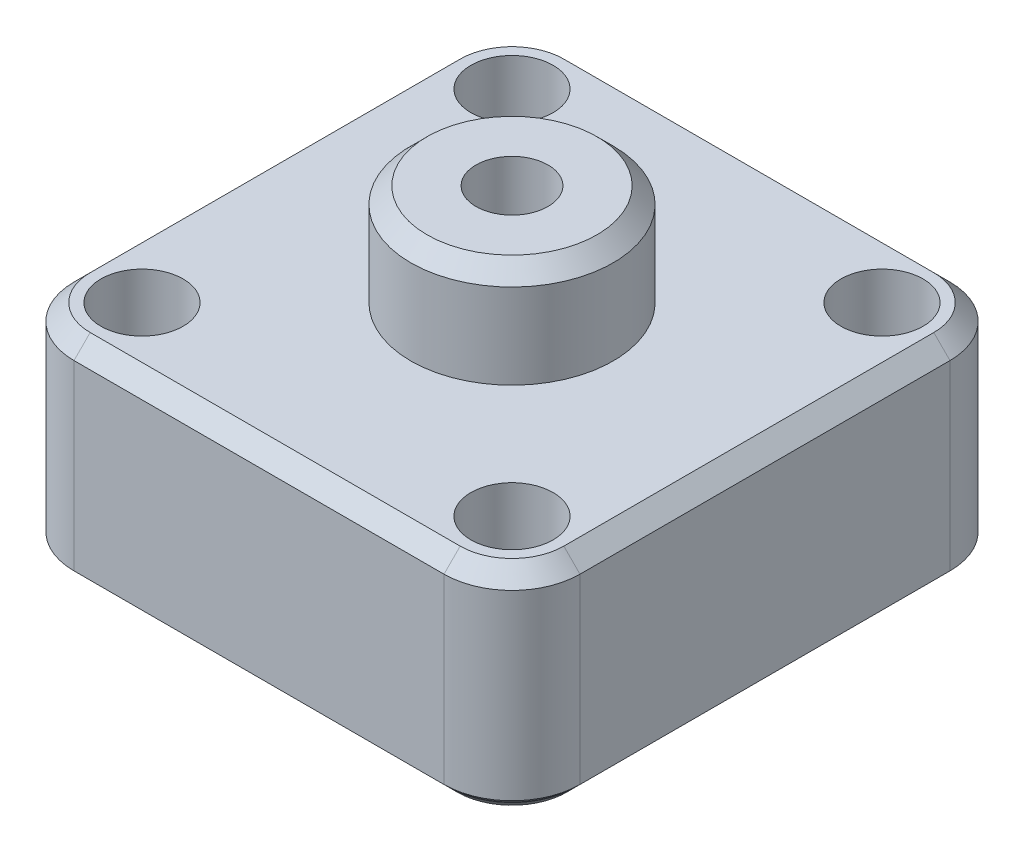
SolidWorks part; units mm, degrees
ref_plane "Front Plane" through (0, 0, 0) normal (0, 0, 1) x (1, 0, 0)
ref_plane "Top Plane" through (0, 0, 0) normal (0, 1, 0) x (1, 0, 0)
ref_plane "Right Plane" through (0, 0, 0) normal (1, 0, 0) x (0, 0, -1)
sketch "Sketch1" plane through (0, 0, 0) normal (0, 1, 0) x (1, 0, 0)
  line L1 (-7.9375, 7.9375) -> (7.9375, 7.9375)
  line L2 (-7.9375, 7.9375) -> (-7.9375, -7.9375)
  line L3 (-7.9375, -7.9375) -> (7.9375, -7.9375)
  line L4 (7.9375, 7.9375) -> (7.9375, -7.9375)
  line L5 (-7.9375, 7.9375) -> (7.9375, -7.9375) construction
  line L6 (-7.9375, -7.9375) -> (7.9375, 7.9375) construction
  point P0 (0, 0)
  dimension "D1" = 15.875
  dimension "D2" = 15.875
extrude "Boss-Extrude1" add sketch "Sketch1" along normal blind 9.525
hole_wizard "#5-40 Tapped Hole1" positions "Sketch2" profile "Sketch3" tap size "#5-40" standard "ANSI Inch" end condition through all
sketch "Sketch2" plane through (0, 0, 0) normal (0, -1, 0) x (-1, 0, 0)
  line L0 (-5.8039, 5.8039) -> (5.8039, -5.8039) construction
  point P0 (-5.8039, -5.8039)
  point P2 (-5.8039, 5.8039)
  point P4 (5.8039, 5.8039)
  point P6 (5.8039, -5.8039)
  dimension "D1" = 11.6078
  dimension "D2" = 11.6078
sketch "Sketch3" plane through (5.8039, 0, 5.8039) normal (1, 0, 0) x (0, 0, -1)
  line L0 (0, 0) -> (0, 9.525)
  line L1 (0, 9.525) -> (1.289, 9.525)
  line L2 (1.289, 9.525) -> (1.289, 0)
  line L5 (1.289, 0) -> (0, 0)
  line L11 (0, -6.35) -> (0, 107.95) construction
  dimension "Thru Tap Drill Dia." = 2.5781
  dimension "Thru Tap Drill Depth" = 9.525
cosmetic thread "Hole Thread1" parameters "D2"=3.175
cosmetic thread "Hole Thread2" parameters "D2"=3.175
cosmetic thread "Hole Thread3" parameters "D2"=3.175
cosmetic thread "Hole Thread4" parameters "D2"=3.175
sketch "Sketch4" plane through (0, 0, 0) normal (0, -1, 0) x (1, 0, 0)
  circle A0 centre (0, 0) radius 3.937
  dimension "D1" = 7.874
extrude "Boss-Extrude2" add sketch "Sketch4" along normal blind 1.143
sketch "Sketch10" plane through (0, -1.143, 0) normal (0, -1, 0) x (1, 0, 0)
  circle A0 centre (0, 0) radius 1.9685
  dimension "D1" = 3.937
extrude "Boss-Extrude4" add sketch "Sketch10" along normal offset from surface (4.953 mm away) 6.096 up to face at (0, 0, 3.937) offset beyond the face yes
hole_wizard "#4-40 Tapped Hole1" positions "Sketch5" profile "Sketch6" tap size "#4-40" standard "ANSI Inch" end condition through all
sketch "Sketch5" plane through (0, -6.096, 0) normal (0, -1, 0) x (-1, 0, 0)
  point P0 (0, 0)
sketch "Sketch6" plane through (0, -6.096, 0) normal (1, 0, 0) x (0, 0, -1)
  line L0 (0, 0) -> (0, 15.621)
  line L1 (0, 15.621) -> (1.1303, 15.621)
  line L2 (1.1303, 15.621) -> (1.1303, 0)
  line L5 (1.1303, 0) -> (0, 0)
  line L11 (0, -6.35) -> (0, 107.95) construction
  dimension "Thru Tap Drill Dia." = 2.2606
  dimension "Thru Tap Drill Depth" = 15.621
cosmetic thread "Hole Thread6" parameters "D2"=2.8448
sketch "Sketch8" plane through (0, 9.525, 0) normal (0, 1, 0) x (1, 0, 0)
  arc A0 (-3.8971, 8.3426) -> (-8.3426, 3.8971) centre (-5.8039, 5.8039) ccw
  arc A1 (8.3426, 3.8971) -> (3.8971, 8.3426) centre (5.8039, 5.8039) ccw
  arc A2 (3.8971, -8.3426) -> (8.3426, -3.8971) centre (5.8039, -5.8039) ccw
  arc A3 (-8.3426, -3.8971) -> (-3.8971, -8.3426) centre (-5.8039, -5.8039) ccw
  arc A4 (-3.8971, 8.3426) -> (3.8971, 8.3426) centre (0, 13.5311) ccw
  arc A5 (-8.3426, -3.8971) -> (-8.3426, 3.8971) centre (-13.5311, 0) ccw
  arc A6 (8.3426, 3.8971) -> (8.3426, -3.8971) centre (13.5311, 0) ccw
  arc A7 (3.8971, -8.3426) -> (-3.8971, -8.3426) centre (0, -13.5311) ccw
  dimension "D1" = 3.175
extrude "Cut-Extrude2" [suppressed] cut sketch "Sketch8" against normal through all flip side to cut
sketch "Sketch9" plane through (0, 9.525, 0) normal (0, 1, 0) x (1, 0, 0)
  circle A0 centre (0, 0) radius 3.175
  dimension "D1" = 6.35
extrude "Cut-Extrude3" cut sketch "Sketch9" against normal offset from surface (3.175 mm away) 6.35 flip side to cut up to face at (0, 0, 3.937)
sketch "Sketch11" plane through (0, 0, 0) normal (0, -1, 0) x (1, 0, 0)
  line L0 (-5.8039, 7.9375) -> (5.8039, 7.9375)
  line L1 (7.9375, 5.8039) -> (7.9375, -5.8039)
  line L2 (5.8039, -7.9375) -> (-5.8039, -7.9375)
  line L3 (-7.9375, 5.8039) -> (-7.9375, -5.8039)
  line L4 (7.9375, 7.9375) -> (7.9375, -7.9375) construction
  arc A0 (7.9375, 5.8039) -> (5.8039, 7.9375) centre (5.8039, 5.8039) ccw
  arc A1 (-5.8039, 7.9375) -> (-7.9375, 5.8039) centre (-5.8039, 5.8039) ccw
  arc A2 (-7.9375, -5.8039) -> (-5.8039, -7.9375) centre (-5.8039, -5.8039) ccw
  arc A3 (5.8039, -7.9375) -> (7.9375, -5.8039) centre (5.8039, -5.8039) ccw
extrude "Cut-Extrude4" cut sketch "Sketch11" against normal through all flip side to cut
chamfer "Chamfer1" distance 0.254 angle 45 2 edges at (0, -1.143, -3.937) (0, -6.096, 1.9685)
chamfer "Chamfer3" distance 0.508 angle 45 9 edges at (7.9375, 6.35, 0) (7.3126, 6.35, -7.3126) (7.3126, 6.35, 7.3126) (0, 6.35, -7.9375) (0, 6.35, 7.9375) (-7.3126, 6.35, -7.3126) (-7.3126, 6.35, 7.3126) (-7.9375, 6.35, 0) (0, 9.525, 3.175)
chamfer "Chamfer4" distance 0.127 angle 45 8 edges at (-7.9375, 0, 0) (-7.3126, 0, 7.3126) (-7.3126, 0, -7.3126) (0, 0, 7.9375) (0, 0, -7.9375) (7.3126, 0, 7.3126) (7.3126, 0, -7.3126) (7.9375, 0, 0)
